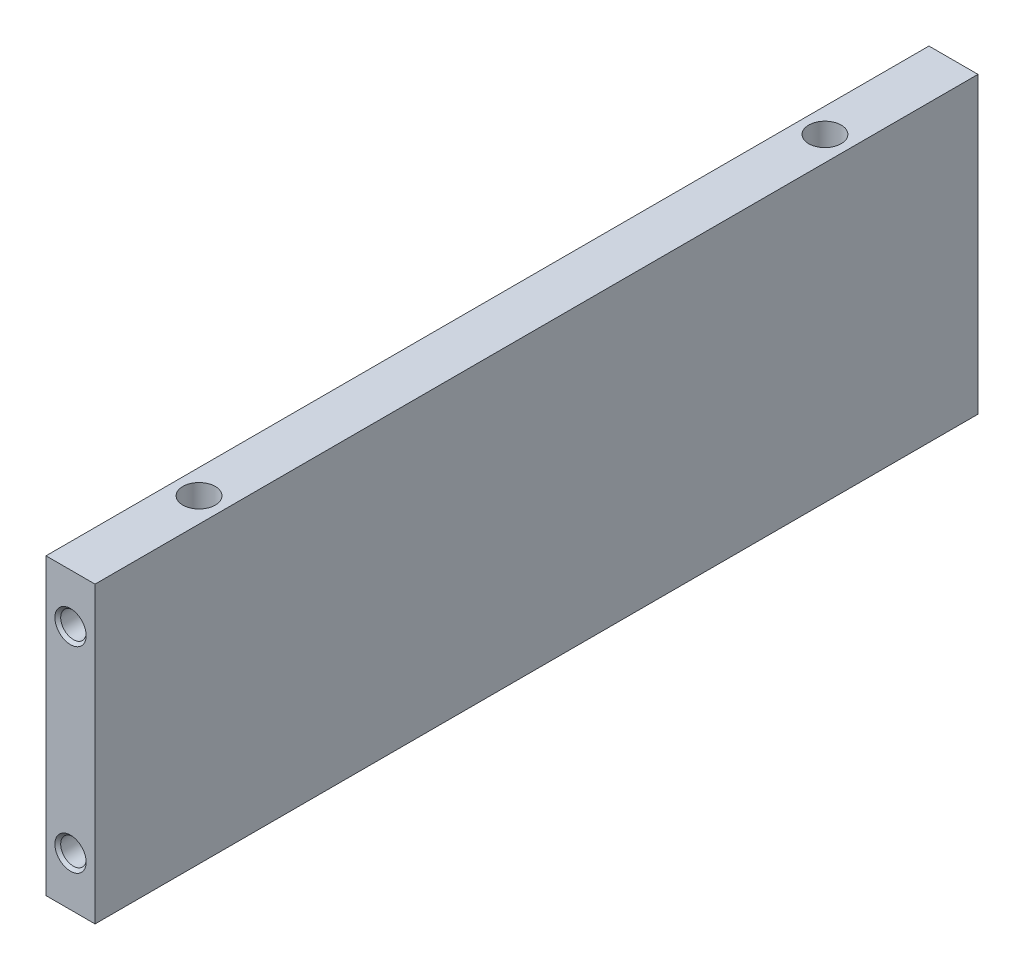
SolidWorks part; units mm, degrees
material "ASTM A36 Steel"
ref_plane "Front Plane" through (0, 0, 0) normal (0, 0, 1) x (1, 0, 0)
ref_plane "Top Plane" through (0, 0, 0) normal (0, 1, 0) x (1, 0, 0)
ref_plane "Right Plane" through (0, 0, 0) normal (1, 0, 0) x (0, 0, -1)
sketch "Sketch1" plane through (0, 0, 0) normal (0, 0, 1) x (1, 0, 0)
  line L1 (-3.175, 19.05) -> (3.175, 19.05)
  line L2 (-3.175, 19.05) -> (-3.175, -19.05)
  line L3 (-3.175, -19.05) -> (3.175, -19.05)
  line L4 (3.175, 19.05) -> (3.175, -19.05)
  line L5 (-3.175, 19.05) -> (3.175, -19.05) construction
  line L6 (-3.175, -19.05) -> (3.175, 19.05) construction
  point P0 (0, 0)
  dimension "D1" = 38.1
  dimension "D2" = 6.35
extrude "Boss-Extrude1" add sketch "Sketch1" along normal blind 57.15 and the other way blind 57.15
sketch "Sketch2" plane through (0, 19.05, 0) normal (0, 1, 0) x (1, 0, 0)
  line L0 (3.175, 57.15) -> (3.175, -57.15) construction
  circle A0 centre (0, 40.513) radius 2.1
  circle A1 centre (0, -40.513) radius 2.1
  dimension "D1" = 4.2
  dimension "D2" = 4.2
  dimension "D3" = 3.175
  dimension "D4" = 40.513
  dimension "D5" = 40.513
  dimension "D6" = 3.175
extrude "Cut-Extrude2" cut sketch "Sketch2" against normal through all contours A1 | A0
sketch "Sketch3" plane through (0, 0, 57.15) normal (0, 0, 1) x (1, 0, 0)
  line L0 (3.175, -19.05) -> (3.175, 19.05) construction
  line L1 (2.1, 19.05) -> (-2.1, 19.05) construction
  line L2 (-3.175, -19.05) -> (3.175, -19.05) construction
  circle A0 centre (0, 12.7) radius 2
  circle A1 centre (0, -12.7) radius 2
  dimension "D1" = 4
  dimension "D2" = 4
  dimension "D3" = 3.175
  dimension "D4" = 3.175
  dimension "D5" = 6.35
  dimension "D6" = 6.35
hole_wizard "Trou taraudé M4x0.71" positions "Esquisse1" profile "Esquisse2" tap size "M4x0.7" standard "Ansi Metric" end condition up to next
sketch "Esquisse1" plane through (0, 0, 57.15) normal (0, 0, 1) x (1, 0, 0)
  point P0 (0, 12.7)
  point P3 (0, -12.7)
sketch "Esquisse2" plane through (0, 12.7, 57.15) normal (1, 0, 0) x (0, -1, 0)
  line L0 (0, 0) -> (0, 14.537)
  line L1 (0, 14.537) -> (1.65, 14.537)
  line L2 (1.65, 14.537) -> (1.65, 0.375)
  line L3 (1.65, 0.375) -> (2.025, 0)
  line L5 (2.025, 0) -> (0, 0)
  line L6 (-1.65, 0.375) -> (-2.025, 0) construction
  line L11 (0, -6.35) -> (0, 107.95) construction
  dimension "Diamètre du trou pour taraudage jusqu'au prochain" = 3.3
  dimension "Profondeur du trou pour taraudage jusqu'au prochain" = 14.537
  dimension "Diamètre du fraisage entrant" = 4.05
  dimension "Angle du fraisage entrant" = 90
cosmetic thread "Filetage de perçage1" parameters "D2"=4
cosmetic thread "Filetage de perçage2" parameters "D2"=4
mirror "Symétrie1" about plane through (0, 0, 0) normal (0, 0, 1) of "Trou taraudé M4x0.71"
cosmetic thread "Filetage de perçage3" parameters "D2"=4
cosmetic thread "Filetage de perçage4" parameters "D2"=4
equation "\"D4@Sketch2\"=3.19/2"
equation "\"D5@Sketch2\"=3.19/2"
